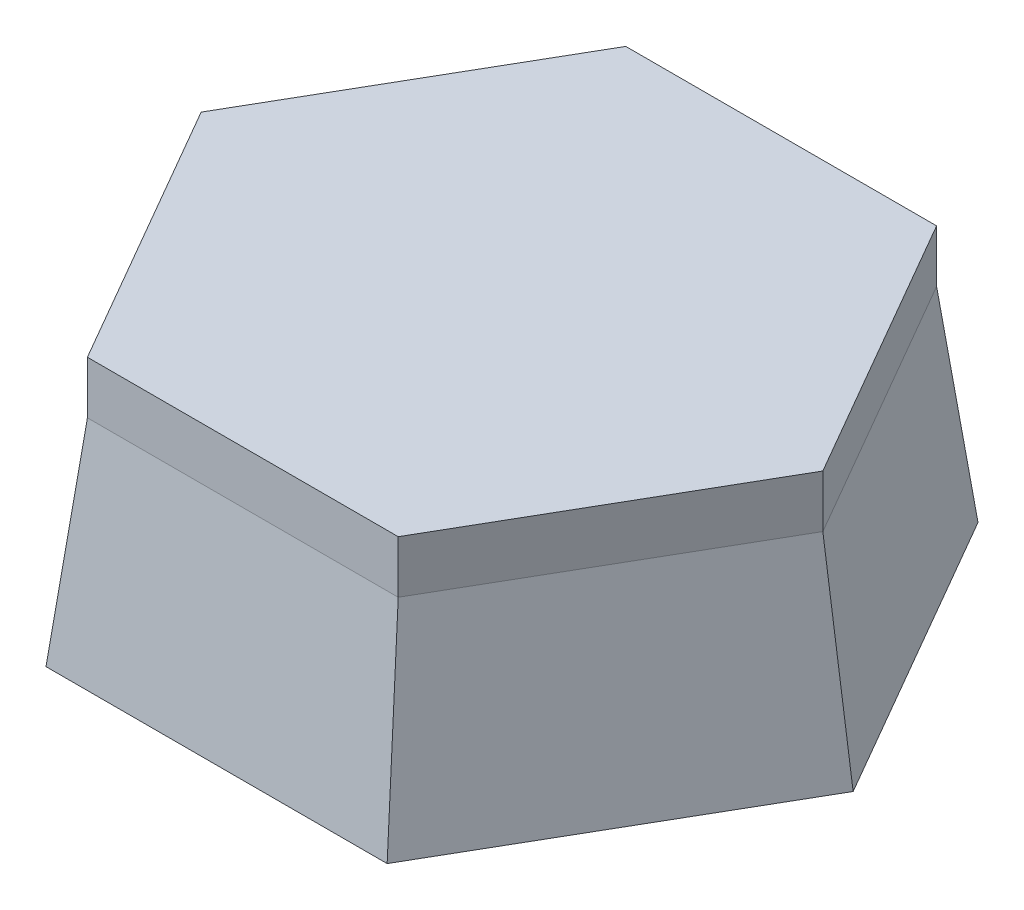
SolidWorks part; units mm, degrees
ref_plane "Front Plane" through (0, 0, 0) normal (0, 0, 1) x (1, 0, 0)
ref_plane "Top Plane" through (0, 0, 0) normal (0, 1, 0) x (1, 0, 0)
ref_plane "Right Plane" through (0, 0, 0) normal (1, 0, 0) x (0, 0, -1)
sketch "Sketch1" plane through (0, 0, 0) normal (0, 1, 0) x (1, 0, 0)
  line L1 (26, 0) -> (13, 22.5167)
  line L2 (13, 22.5167) -> (-13, 22.5167)
  line L3 (-13, 22.5167) -> (-26, 0)
  line L4 (-26, 0) -> (-13, -22.5167)
  line L5 (-13, -22.5167) -> (13, -22.5167)
  line L6 (13, -22.5167) -> (26, 0)
  circle A0 centre (0, 0) radius 22.5167 construction
  dimension "D1" = 52
ref_plane "Plane1" through (0, 16, 0) normal (0, 1, 0) x (1, 0, 0)
sketch "Sketch2" plane through (0, 16, 0) normal (0, 1, 0) x (1, 0, 0)
  line L1 (23.69, 0) -> (11.845, 20.5161)
  line L2 (11.845, 20.5161) -> (-11.845, 20.5161)
  line L3 (-11.845, 20.5161) -> (-23.69, 0)
  line L4 (-23.69, 0) -> (-11.845, -20.5161)
  line L5 (-11.845, -20.5161) -> (11.845, -20.5161)
  line L6 (11.845, -20.5161) -> (23.69, 0)
  circle A0 centre (0, 0) radius 20.5161 construction
  dimension "D1" = 47.38
loft "Loft1" add profiles "Sketch2", "Sketch1" connector at (-23.69, 16, 0) connector at (-26, 0, 0)
sketch "Sketch3" plane through (0, 16, 0) normal (0, 1, 0) x (1, 0, 0)
  line L0 (23.69, 0) -> (11.845, 20.5161) construction
  line L1 (11.845, -20.5161) -> (23.69, 0) construction
  line L2 (-11.845, -20.5161) -> (11.845, -20.5161) construction
  line L3 (-23.69, 0) -> (-11.845, -20.5161) construction
  line L4 (-11.845, 20.5161) -> (-23.69, 0) construction
  line L5 (11.845, 20.5161) -> (-11.845, 20.5161) construction
  line L6 (23.69, 0) -> (11.845, 20.5161)
  line L7 (11.845, -20.5161) -> (23.69, 0)
  line L8 (-11.845, -20.5161) -> (11.845, -20.5161)
  line L9 (-23.69, 0) -> (-11.845, -20.5161)
  line L10 (-11.845, 20.5161) -> (-23.69, 0)
  line L11 (11.845, 20.5161) -> (-11.845, 20.5161)
extrude "Boss-Extrude1" add sketch "Sketch3" along normal blind 4
ref_plane "Plane2" through (0, -2, 0) normal (0, -1, 0) x (-1, 0, 0)
sketch "Sketch4" plane through (0, -2, 0) normal (0, -1, 0) x (-1, 0, 0)
  line L1 (23, 0) -> (11.5, 19.9186)
  line L2 (11.5, 19.9186) -> (-11.5, 19.9186)
  line L3 (-11.5, 19.9186) -> (-23, 0)
  line L4 (-23, 0) -> (-11.5, -19.9186)
  line L5 (-11.5, -19.9186) -> (11.5, -19.9186)
  line L6 (11.5, -19.9186) -> (23, 0)
  circle A0 centre (0, 0) radius 19.9186 construction
  dimension "D1" = 46
ref_plane "Plane3" through (0, 16, 0) normal (0, -1, 0) x (-1, 0, 0)
sketch "Sketch5" plane through (0, 16, 0) normal (0, -1, 0) x (-1, 0, 0)
  line L1 (20.69, 0) -> (10.345, 17.9181)
  line L2 (10.345, 17.9181) -> (-10.345, 17.9181)
  line L3 (-10.345, 17.9181) -> (-20.69, 0)
  line L4 (-20.69, 0) -> (-10.345, -17.9181)
  line L5 (-10.345, -17.9181) -> (10.345, -17.9181)
  line L6 (10.345, -17.9181) -> (20.69, 0)
  circle A0 centre (0, 0) radius 17.9181 construction
  dimension "D1" = 41.38
loft "Cut-Loft1" cut profiles "Sketch5", "Sketch4" connector at (10.345, 16, 17.9181) connector at (11.5, -2, 19.9186)
